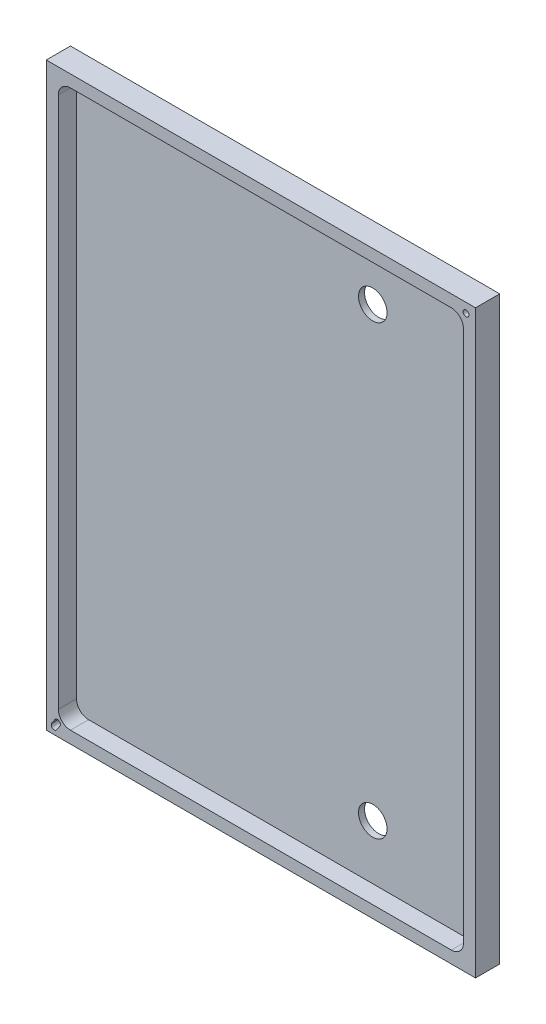
SolidWorks part; units mm, degrees
material "AISI 304"
ref_plane "Front Plane" through (0, 0, 0) normal (0, 0, 1) x (1, 0, 0)
ref_plane "Top Plane" through (0, 0, 0) normal (0, 1, 0) x (1, 0, 0)
ref_plane "Right Plane" through (0, 0, 0) normal (1, 0, 0) x (0, 0, -1)
sketch "Sketch1" plane through (0, 0, 0) normal (0, 0, 1) x (1, 0, 0)
  line L1 (112.7125, -152.4) -> (-112.7125, -152.4)
  line L2 (112.7125, -152.4) -> (112.7125, 152.4)
  line L3 (112.7125, 152.4) -> (-112.7125, 152.4)
  line L4 (-112.7125, -152.4) -> (-112.7125, 152.4)
  line L5 (112.7125, -152.4) -> (-112.7125, 152.4) construction
  line L6 (112.7125, 152.4) -> (-112.7125, -152.4) construction
  point P0 (0, 0)
  dimension "D1" = 304.8
  dimension "D2" = 225.425
extrude "Boss-Extrude1" add sketch "Sketch1" along normal blind 12.7
sketch "Sketch2" plane through (0, 0, 12.7) normal (0, 0, 1) x (1, 0, 0)
  line L0 (-112.7125, 152.4) -> (-112.7125, -152.4) construction
  line L1 (100.0125, -146.05) -> (-100.0125, -146.05)
  line L2 (106.3625, -139.7) -> (106.3625, 139.7)
  line L3 (100.0125, 146.05) -> (-100.0125, 146.05)
  line L4 (-106.3625, -139.7) -> (-106.3625, 139.7)
  line L5 (106.3625, -146.05) -> (-106.3625, 146.05) construction
  line L6 (106.3625, 146.05) -> (-106.3625, -146.05) construction
  line L7 (112.7125, 152.4) -> (-112.7125, 152.4) construction
  arc A0 (-100.0125, -146.05) -> (-106.3625, -139.7) centre (-100.0125, -139.7) cw
  arc A1 (100.0125, -146.05) -> (106.3625, -139.7) centre (100.0125, -139.7) ccw
  arc A2 (106.3625, 139.7) -> (100.0125, 146.05) centre (100.0125, 139.7) ccw
  arc A3 (-100.0125, 146.05) -> (-106.3625, 139.7) centre (-100.0125, 139.7) ccw
  point P0 (0, 0)
  dimension "D3" = 6.35
  dimension "D1" = 6.35
  dimension "D2" = 6.35
extrude "Cut-Extrude1" cut sketch "Sketch2" against normal blind 9.525
sketch "Sketch4" plane through (0, 0, 0) normal (0, 0, -1) x (-1, 0, 0)
  line L0 (112.7125, -152.4) -> (-112.7125, -152.4) construction
  line L1 (-112.7125, -152.4) -> (-112.7125, 152.4) construction
  line L2 (0, 0) -> (-117.2439, 0) construction
  circle A0 centre (-49.2125, -117.4) radius 7.5
  circle A1 centre (-49.2125, 117.4) radius 7.5
  dimension "D1" = 15
  dimension "D2" = 35
  dimension "D3" = 63.5
  dimension "D4" = 0
extrude "Cut-Extrude3" cut sketch "Sketch4" against normal through all
hole_wizard "Ø3.1 (3.1) Diameter Hole1" positions "Sketch7" profile "Sketch8" hole size "Ø3.1" standard "ANSI Metric"
sketch "Sketch7" plane through (0, 0, 12.7) normal (0, 0, 1) x (1, 0, 0)
  line L0 (112.7125, -152.4) -> (112.7125, 152.4) construction
  line L1 (112.7125, 152.4) -> (-112.7125, 152.4) construction
  point P0 (107.7125, 147.4)
  dimension "D1" = 5
  dimension "D2" = 5
sketch "Sketch8" plane through (107.7125, 147.4, 12.7) normal (1, 0, 0) x (0, -1, 0)
  line L0 (0, 0) -> (0, 5.9313)
  line L1 (0, 5.9313) -> (1.55, 5)
  line L2 (1.55, 5) -> (1.55, 0)
  line L5 (1.55, 0) -> (0, 0)
  line L10 (0, 5.9313) -> (-1.55, 5) construction
  line L11 (0, -6.35) -> (0, 107.95) construction
  dimension "Hole Dia." = 3.1
  dimension "Hole Depth" = 5
  dimension "Drill Angle" = 118
sketch "Sketch9" plane through (0, 0, 12.7) normal (0, 0, 1) x (1, 0, 0)
  line L0 (-108.5404, -148.6508) -> (-106.8846, -146.1492) construction
  line L1 (-109.8329, -147.7953) -> (-108.1771, -145.2937)
  line L2 (-107.2479, -149.5063) -> (-105.5921, -147.0047)
  line L3 (-112.7125, -152.4) -> (112.7125, -152.4) construction
  line L4 (-112.7125, 152.4) -> (-112.7125, -152.4) construction
  arc A0 (-109.8329, -147.7953) -> (-107.2479, -149.5063) centre (-108.5404, -148.6508) ccw
  arc A1 (-105.5921, -147.0047) -> (-108.1771, -145.2937) centre (-106.8846, -146.1492) ccw
  point P4 (-107.7125, -147.4)
  dimension "D1" = 3.1
  dimension "D2" = 5
  dimension "D3" = 5
  dimension "D4" = 3
  dimension "D5" = 56.5
extrude "Cut-Extrude4" cut sketch "Sketch9" against normal blind 5
hole_wizard "M4x0.7 Tapped Hole1" positions "Sketch10" profile "Sketch11" tap size "M4x0.7" standard "ANSI Metric"
sketch "Sketch10" plane through (0, 0, 0) normal (0, 0, -1) x (-1, 0, 0)
  line L0 (112.7125, 152.4) -> (112.7125, -152.4) construction
  line L1 (-112.7125, 152.4) -> (112.7125, 152.4) construction
  point P0 (109.5375, -113.6)
  point P2 (109.5375, 113.6)
  dimension "D1" = 3.175
  dimension "D2" = 38.8
  dimension "D3" = 266
sketch "Sketch11" plane through (-109.5375, -113.6, 0) normal (1, 0, 0) x (0, 1, 0)
  line L0 (0, 0) -> (0, 6.3914)
  line L1 (0, 6.3914) -> (1.65, 5.4)
  line L2 (1.65, 5.4) -> (1.65, 0)
  line L5 (1.65, 0) -> (0, 0)
  line L10 (0, 6.3914) -> (-1.65, 5.4) construction
  line L11 (0, -6.35) -> (0, 107.95) construction
  dimension "Tap Drill Dia." = 3.3
  dimension "Tap Drill Depth" = 5.4
  dimension "Drill Angle" = 118
cosmetic thread "Hole Thread1" parameters "D1"=3, "D2"=4.3
cosmetic thread "Hole Thread2" parameters "D1"=3, "D2"=4.3
